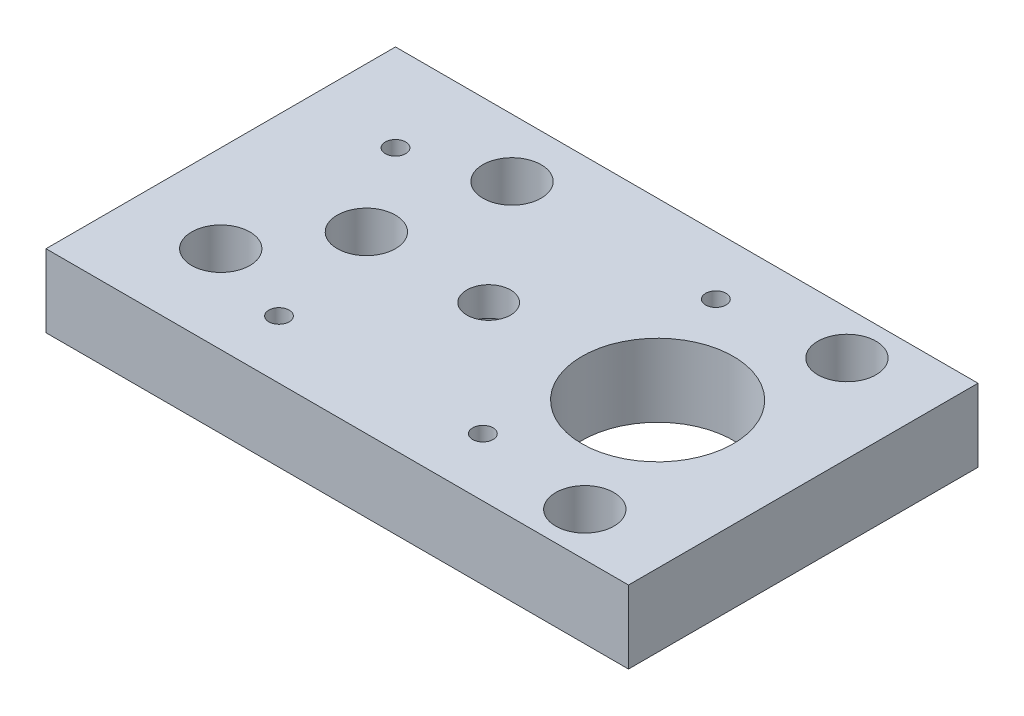
SolidWorks part; units mm, degrees
ref_plane "前视基准面" through (0, 0, 0) normal (0, 0, 1) x (1, 0, 0)
ref_plane "上视基准面" through (0, 0, 0) normal (0, 1, 0) x (1, 0, 0)
ref_plane "右视基准面" through (0, 0, 0) normal (1, 0, 0) x (0, 0, -1)
other "Configuration Table"
sketch "草图1" plane through (0, 0, 0) normal (0, 1, 0) x (1, 0, 0)
  line L0 (7.8359, -6) -> (30.681, -6) construction
  line L1 (0, 0) -> (20, 0)
  line L2 (0, 0) -> (0, -12)
  line L3 (0, -12) -> (20, -12)
  line L4 (20, 0) -> (20, -12)
  circle A3 centre (9.2, -6) radius 1.6
  circle A5 centre (15, -6) radius 2.6
  circle A6 centre (9.2, -6) radius 0.75
  circle A7 centre (5, -6) radius 1
  point P5 (5, -6)
  point P10 (0, 0)
  point P11 (2.2151, -6)
  point P17 (0, 0)
  dimension "D4" = 5.8
  dimension "D6" = 3.2
  dimension "D8" = 2
  dimension "D11" = 5.2
  dimension "D13" = 1.5
  dimension "D2" = 5
  dimension "D3" = 4.2
  dimension "D5" = 10
  dimension "D7" = 20
  dimension "D9" = 6
  dimension "D10" = 5
  dimension "D12" = 12
extrude "凸台-拉伸1" add sketch "草图1" along normal blind 2.5 contours L4 L3 L2 L1 | A3 | A5 | A7
extrude "凸台-拉伸2" add sketch "草图1<5>" against normal blind 1 from surface contours A3 | A6 starting at face at (10, 2.5, 6)
sketch "草图1<5>" plane through (0, 0, 0) normal (0, 1, 0) x (1, 0, 0) same geometry as "草图1"
sketch "草图3" plane through (0, 2.5, 0) normal (0, 1, 0) x (1, 0, 0)
  line L0 (0, 0) -> (0, -12) construction
  line L1 (0, 0) -> (20, 0) construction
  line L2 (0, -12) -> (20, -12) construction
  line L3 (20, 0) -> (20, -12) construction
  circle A0 centre (6, -2) radius 1
  circle A1 centre (3, -9) radius 1
  circle A2 centre (17, -1.5) radius 1
  circle A3 centre (17, -10.5) radius 1
  circle A4 centre (3, -9) radius 0.7
  circle A5 centre (6, -2) radius 0.7
  circle A6 centre (17, -1.5) radius 0.7
  circle A7 centre (17, -10.5) radius 0.7
  circle A11 centre (3, -3) radius 0.35
  circle A12 centre (6, -10) radius 0.35
  circle A13 centre (13, -10) radius 0.35
  circle A14 centre (13, -2) radius 0.35
  circle A21 centre (3, -9) radius 0.35 construction
  point P24 (0, 0)
  point P29 (0.7, -11.1321)
  point P32 (0, 0)
  point P33 (0, 0)
  point P34 (-3.7043, -9.3)
  point P35 (0, 0)
  point P36 (0, 0)
  point P37 (5.7918, -10.0578)
  point P38 (0, 0)
  point P39 (0, 0)
  point P40 (0, 0)
  dimension "D1" = 1.4
  dimension "D2" = 2
  dimension "D3" = 0.7
  dimension "D4" = 3
  dimension "D5" = 3
  dimension "D6" = 2
  dimension "D7" = 6
  dimension "D8" = 7
  dimension "D9" = 2
  dimension "D10" = 7
  dimension "D11" = 2
extrude "切除-拉伸1" cut sketch "草图3" against normal through all contours A5 | A4 | A6 | A7 | A12 | A11 | A14 | A13
extrude "切除-拉伸2" cut sketch "草图3<3>" against normal blind 1.5 contours A0 | A1 | A3 | A2
sketch "草图3<3>" plane through (0, 2.5, 0) normal (0, 1, 0) x (1, 0, 0) same geometry as "草图3"
